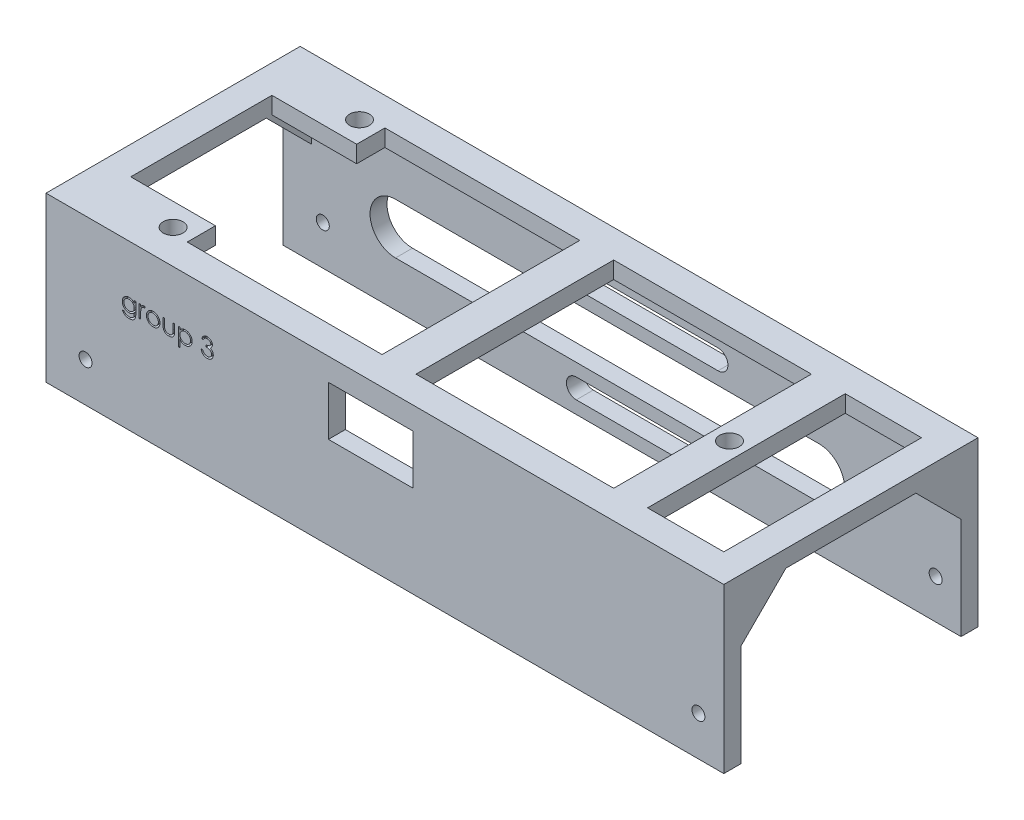
SolidWorks part; units mm, degrees
other "Markup1"
sketch "Sketch23" plane through (120, 29, 45) normal (0.0467, 0.9512, 0.3049) x (0.9885, 0, -0.1514)
sketch "Sketch24" plane through (120, 29, 45) normal (0.0467, 0.9512, 0.3049) x (0.9885, 0, -0.1514)
sketch "Sketch25" plane through (120, 29, 45) normal (0.0467, 0.9512, 0.3049) x (0.9885, 0, -0.1514)
sketch "Sketch26" plane through (120, 29, 45) normal (0.0467, 0.9512, 0.3049) x (0.9885, 0, -0.1514)
ref_plane "Front Plane" through (0, 0, 0) normal (0, 0, 1) x (1, 0, 0)
ref_plane "Top Plane" through (0, 0, 0) normal (0, 1, 0) x (1, 0, 0)
ref_plane "Right Plane" through (0, 0, 0) normal (1, 0, 0) x (0, 0, -1)
sketch "Sketch1" plane through (0, 0, 0) normal (0, 0, 1) x (1, 0, 0)
  line L9 (21.172, -17.9478) -> (91.172, -17.9478)
  line L10 (21.172, -17.9478) -> (21.172, -40.3878)
  line L11 (4, -8) -> (200.227, -8) construction
  line L12 (4, -8) -> (-67.5185, -8) construction
  line L13 (21.172, -40.3878) -> (91.172, -40.3878)
  line L14 (91.172, -17.9478) -> (91.172, -40.3878)
  line L15 (0, 0) -> (120, 0)
  line L16 (0, 0) -> (0, 29)
  line L17 (0, 29) -> (120, 29)
  line L18 (120, 0) -> (120, 29)
  circle A0 centre (4, 7) radius 1.15
  circle A1 centre (4, 7) radius 15 construction
  circle A3 centre (77.172, -29.1678) radius 3.6067
  circle A4 centre (116, 7) radius 15 construction
  circle A5 centre (116, 7) radius 1.15
  point P19 (21.172, -29.1678)
  dimension "D4" = 30
  dimension "D2" = 14
  dimension "D7" = 30
  dimension "D11" = 4
  dimension "D13" = 2.3
  dimension "D14" = 2.3
  dimension "D3" = 70
  dimension "D5" = 22.44
  dimension "D6" = 120
  dimension "D8" = 29
  dimension "D9" = 4
  dimension "D10" = 7
  dimension "D12" = 7
extrude "Boss-Extrude5" add sketch "Sketch1" along normal blind 45 contours L16 L15 L18 L17
shell "Shell9" thickness 3 removed face at (120, 14.5, 22.5) removed face at (60, 0, 22.5) removed face at (0, 14.5, 22.5)
sketch "Sketch3" plane through (0, 0, 0) normal (0, 0, -1) x (-1, 0, 0)
  line L0 (0, 0) -> (-120, 0) construction
  line L1 (-120, 0) -> (-120, 29) construction
  line L2 (0, 0) -> (0, 29) construction
  circle A0 centre (-7, 7) radius 1.15
  circle A1 centre (-115.5, 7) radius 1.15
  dimension "D1" = 2.3
  dimension "D2" = 2.3
  dimension "D3" = 7
  dimension "D4" = 4.5
  dimension "D5" = 7
  dimension "D6" = 7
extrude "Cut-Extrude2" cut sketch "Sketch3" against normal blind 79
sketch "Sketch6" plane through (0, 0, 0) normal (0, 0, -1) x (-1, 0, 0)
  line L0 (-76.9735, 21) -> (-51.8835, 21) construction
  line L1 (-76.9735, 22.75) -> (-51.8835, 22.75)
  line L2 (-76.9735, 19.25) -> (-51.8835, 19.25)
  line L7 (41.5249, -18.7743) -> (41.5249, -41.2143) construction
  line L8 (-94.8735, 12.5) -> (-19.8735, 12.5) construction
  line L9 (-94.8735, 17) -> (-19.8735, 17)
  line L10 (-94.8735, 8) -> (-19.8735, 8)
  line L11 (-19.8735, 12.5) -> (-17.326, 12.5) construction
  line L12 (-76.9735, 4) -> (-51.8835, 4) construction
  line L13 (-76.9735, 2.25) -> (-51.8835, 2.25)
  line L14 (-76.9735, 5.75) -> (-51.8835, 5.75)
  line L15 (4.7849, -29.9943) -> (74.7849, -29.9943) construction
  line L20 (4.7849, -18.7743) -> (74.7849, -18.7743)
  line L21 (4.7849, -18.7743) -> (4.7849, -41.2143)
  line L22 (4.7849, -41.2143) -> (74.7849, -41.2143)
  line L23 (74.7849, -18.7743) -> (74.7849, -41.2143)
  line L24 (-120, 0) -> (-120, 29) construction
  line L25 (63.3749, -18.7743) -> (63.3749, -41.2143) construction
  line L26 (0, 29) -> (-120, 29) construction
  arc A4 (-94.8735, 17) -> (-94.8735, 8) centre (-94.8735, 12.5) ccw
  arc A5 (-76.9735, 22.75) -> (-76.9735, 19.25) centre (-76.9735, 21) ccw
  arc A6 (-51.8835, 19.25) -> (-51.8835, 22.75) centre (-51.8835, 21) ccw
  arc A7 (-19.8735, 8) -> (-19.8735, 17) centre (-19.8735, 12.5) ccw
  arc A8 (-76.9735, 2.25) -> (-76.9735, 5.75) centre (-76.9735, 4) cw
  arc A9 (-51.8835, 5.75) -> (-51.8835, 2.25) centre (-51.8835, 4) cw
  circle A15 centre (16.1349, -29.9943) radius 1.5
  circle A16 centre (36.3249, -21.4943) radius 1.5
  circle A17 centre (36.3249, -38.4943) radius 1.5
  circle A18 centre (36.3249, -38.4943) radius 1.5
  circle A19 centre (27.0349, -29.9943) radius 2.3201
  point P11 (-64.4285, 21)
  point P19 (-57.3735, 12.5)
  point P31 (-64.4285, 4)
  dimension "D8" = 1.75
  dimension "D13" = 4.5
  dimension "D10" = 3
  dimension "D14" = 3
  dimension "D9" = 25.09
  dimension "D2" = 8.5
  dimension "D3" = 17.9
  dimension "D4" = 70
  dimension "D5" = 22.44
  dimension "D6" = 36.74
  dimension "D7" = 11.35
  dimension "D11" = 5.2
  dimension "D12" = 8.5
  dimension "D15" = 22.25
  dimension "D16" = 75
  dimension "D17" = 25.1265
  dimension "D18" = 11.41
  dimension "D19" = 16.5
extrude "Cut-Extrude8" cut sketch "Sketch6" against normal blind 23 contours L10 A7 L9 | L2 A6 L1 A5 | L13 A9 L14 A8 region at (64.4285, 21, 0) region at (57.3735, 12.5, 0)
sketch "Sketch7" plane through (0, 0, 45) normal (0, 0, 1) x (1, 0, 0)
  line L1 (50, 25) -> (65, 25)
  line L2 (50, 25) -> (50, 16.25)
  line L3 (50, 16.25) -> (65, 16.25)
  line L4 (65, 25) -> (65, 16.25)
  line L5 (0, 0) -> (120, 0) construction
  line L7 (0, 0) -> (0, 29) construction
  dimension "D1" = 50
  dimension "D2" = 15
  dimension "D3" = 8.75
  dimension "D4" = 25
extrude "Cut-Extrude9" cut sketch "Sketch7" against normal blind 20
sketch "Sketch13" plane through (0, 29, 0) normal (0, 1, 0) x (1, 0, 0)
  line L1 (0, 0) -> (120, 0) construction
  line L4 (5, -5) -> (115, -5)
  line L5 (5, -5) -> (5, -40)
  line L6 (5, -40) -> (115, -40)
  line L8 (0, -45) -> (0, 0) construction
  line L16 (115, -5) -> (115, -40)
  line L17 (120, -45) -> (120, 0) construction
  dimension "D1" = 5
  dimension "D2" = 5
  dimension "D5" = 5
  dimension "D6" = 35
extrude "Cut-Extrude14" cut sketch "Sketch13" against normal blind 10
sketch "Sketch17" plane through (0, 29, 0) normal (0, 1, 0) x (1, 0, 0)
  line L0 (0, -22.5) -> (120, -22.5) construction
  line L1 (5, -5) -> (20, -5)
  line L2 (5, -5) -> (5, -10)
  line L3 (5, -10) -> (20, -10)
  line L4 (20, -5) -> (20, -10)
  line L5 (5, -40) -> (20, -40)
  line L6 (5, -40) -> (5, -35)
  line L7 (5, -35) -> (20, -35)
  line L8 (20, -40) -> (20, -35)
  line L17 (0, -45) -> (0, 0) construction
  line L18 (120, -45) -> (120, 0) construction
  line L25 (115, -5) -> (5, -5) construction
  line L26 (95.5, -5) -> (101.5, -5)
  line L27 (95.5, -5) -> (95.5, -40)
  line L28 (95.5, -40) -> (101.5, -40)
  line L29 (101.5, -5) -> (101.5, -40)
  line L30 (5, -40) -> (115, -40) construction
  line L32 (54.5, -5) -> (60.5, -5)
  line L33 (54.5, -5) -> (54.5, -40)
  line L34 (54.5, -40) -> (60.5, -40)
  line L35 (60.5, -5) -> (60.5, -40)
  circle A0 centre (16.5, -39) radius 1.75
  circle A1 centre (16.5, -6) radius 1.75
  circle A2 centre (98.5, -22.5) radius 1.75
  point P41 (98.5, -5)
  line M10 (5, -40) -> (5, -5)
  line M11 (5, -5) -> (115, -5)
  line M13 (115, -40) -> (5, -40)
  dimension "D3" = 3.5
  dimension "D6" = 3.5
  dimension "D11" = 33
  dimension "D12" = 16.5
  dimension "D13" = 3.5
  dimension "D1" = 5
  dimension "D2" = 15
  dimension "D4" = 5
  dimension "D5" = 15
  dimension "D7" = 6
  dimension "D8" = 18.5
  dimension "D9" = 6
  dimension "D10" = 35
extrude "Boss-Extrude6" add sketch "Sketch17" against normal blind 3 contours A1 L3 L4 M11 M10 | L1 A1 | A0 L8 L7 M13 M10 | L5 A0 | L33 L32 L35 L34 | L27 L26 L29 L28 region at (12.0151, 29, 7.6523) region at (16.5, 29, 6.2435) region at (12.0151, 29, 37.3477) region at (16.5, 29, 38.7565)
extrude "Cut-Extrude16" cut sketch "Sketch17<4>" against normal blind 10 contours A2 L0 | L0 A2 | L1 A1 | L1 A1 | L5 A0 | L5 A0 | A2 region at (98.5, 29, 21.7573) region at (98.5, 29, 23.2427) region at (16.5, 29, 4.6937) region at (16.5, 29, 6.2435) region at (16.5, 29, 38.7565) region at (16.5, 29, 40.3063)
sketch "Sketch17<4>" plane through (0, 29, 0) normal (0, 1, 0) x (1, 0, 0) same geometry as "Sketch17"
sketch "Sketch20" plane through (0, 0, 45) normal (0, 0, 1) x (1, 0, 0)
  line L0 (13.2558, 18.0126) -> (38.9246, 18.0126) construction
  text T0 "group 3"
extrude "Cut-Extrude15" cut sketch "Sketch20" against normal blind 1.5
sketch "Sketch21" plane through (0, 0, 0) normal (-1, 0, 0) x (0, 0, 1)
  line L0 (3, 26) -> (3, 18)
  line L1 (3, 0) -> (3, 26) construction
  line L2 (3, 18) -> (11, 26)
  line L3 (42, 26) -> (3, 26) construction
  line L4 (11, 26) -> (3, 26)
  line L5 (42, 26) -> (34, 26)
  line L6 (34, 26) -> (42, 18)
  line L7 (42, 0) -> (42, 26) construction
  line L8 (42, 18) -> (42, 26)
  dimension "D1" = 8
  dimension "D2" = 8
  dimension "D3" = 8
  dimension "D4" = 8
extrude "Boss-Extrude7" add sketch "Sketch21" against normal blind 5
sketch "Sketch22" plane through (120, 0, 0) normal (1, 0, 0) x (0, 0, -1)
  line L0 (-42, 26) -> (-42, 18)
  line L1 (-42, 18) -> (-34, 26)
  line L2 (-34, 26) -> (-42, 26)
  line L3 (-11, 26) -> (-3, 26)
  line L4 (-3, 26) -> (-3, 18)
  line L5 (-3, 18) -> (-11, 26)
extrude "Boss-Extrude8" add sketch "Sketch22" against normal blind 5
equation "\"slot­_width\"=25.09"
equation "\"D9@Sketch6\"=\"slot­_width\""
